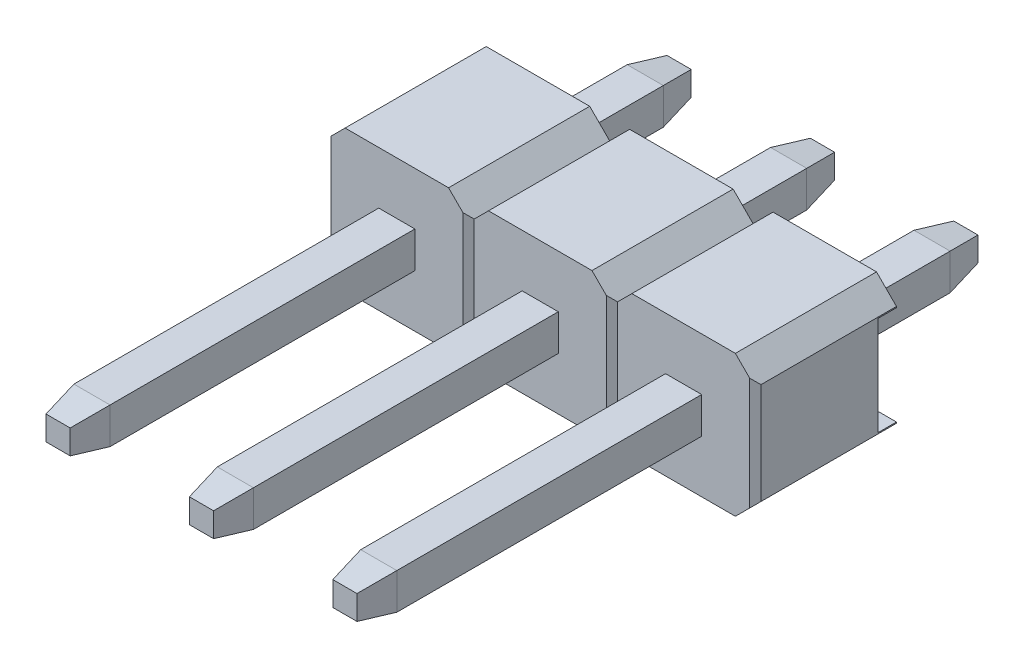
SolidWorks part; units mm, degrees
ref_plane "Front Plane" through (0, 0, 0) normal (0, 0, 1) x (1, 0, 0)
ref_plane "Top Plane" through (0, 0, 0) normal (0, 1, 0) x (1, 0, 0)
ref_plane "Right Plane" through (0, 0, 0) normal (1, 0, 0) x (0, 0, -1)
sketch "Sketch1" plane through (0, 0, 0) normal (0, 0, 1) x (1, 0, 0)
  line L0 (-1.27, 0.8964) -> (-0.9164, 1.25)
  line L1 (-0.9164, 1.25) -> (0.9164, 1.25)
  line L2 (-1.27, 0.8964) -> (-1.27, -0.8964)
  line L3 (-0.9164, -1.25) -> (0.9164, -1.25)
  line L4 (1.27, 0.8964) -> (1.27, -0.8964)
  line L5 (-1.27, -0.8964) -> (-0.9164, -1.25)
  line L6 (0.9164, -1.25) -> (1.27, -0.8964)
  line L7 (1.27, 0.8964) -> (0.9164, 1.25)
  point P0 (1.27, -1.25)
  point P7 (-1.27, 1.25)
  point P10 (-1.27, -1.25)
  point P15 (1.27, 1.25)
  dimension "D5" = 0.25
  dimension "D1" = 2.54
  dimension "D2" = 2.5
  dimension "D3" = 1.27
  dimension "D4" = 1.25
  dimension "D6" = 0.25
  dimension "D7" = 0.25
  dimension "D8" = 0.25
extrude "Extrude1" add sketch "Sketch1" along normal blind 1.25 and the other way blind 1.25
sketch "Sketch4" plane through (0, 0, 0) normal (0, 1, 0) x (1, 0, 0)
  line L0 (-1.27, -1.15) -> (-1.17, -1.25)
  line L1 (-1.17, -1.25) -> (-1.27, -1.25)
  line L2 (-1.27, -1.25) -> (-1.27, -1.15)
  line L3 (1.17, -1.25) -> (1.27, -1.15)
  line L4 (1.27, -1.15) -> (1.27, -1.25)
  line L5 (1.27, -1.25) -> (1.17, -1.25)
extrude "Cut-Extrude3" cut sketch "Sketch4" against normal through all and the other way through all
pattern_linear "LPattern4" count 3 spacing 2.54 along (-1, 0, 0) of "Extrude1", "Cut-Extrude3"
sketch "Sketch2" plane through (0, 0, 0) normal (1, 0, 0) x (0, -1, 0)
  line L1 (-0.8764, 1.25) -> (0.8764, 1.25)
  line L2 (-0.8764, 1.25) -> (-0.8764, 0.92)
  line L3 (-0.8764, 0.92) -> (0.8764, 0.92)
  line L4 (0.8764, 1.25) -> (0.8764, 0.92)
  dimension "D1" = 0.33
extrude "Cut-Extrude1" cut sketch "Sketch2" against normal through all and the other way through all
sketch "Sketch3" plane through (0, 0, 0) normal (1, 0, 0) x (0, 0, -1)
  line L0 (-7.25, 0) -> (3.75, 0)
  line L1 (1.25, 1.25) -> (1.25, 0.8964) construction
  dimension "D1" = 6
  dimension "D2" = 2.5
extrude "Extrude-Thin1" add sketch "Sketch3" along normal blind 0.32 and the other way blind 0.32 thin thin type mid plane wall 0.64
pattern_linear "LPattern5" count 1 spacing 2.54 along (1, 0, 0) count 3 spacing 2.54 along (-1, 0, 0) of "Extrude-Thin1"
chamfer "Chamfer2" distance 0.6 angle 10 24 edges at (0.32, 0, 7.25) (0, -0.32, 7.25) (-0.32, 0, 7.25) (0, 0.32, 7.25) (0.32, 0, -3.75) (-0.32, 0, -3.75) (-4.76, 0, -3.75) (-5.4, 0, -3.75) (-2.22, 0, -3.75) (-2.86, 0, -3.75) (-2.22, 0, 7.25) (-2.54, -0.32, 7.25) (-2.86, 0, 7.25) (-2.54, 0.32, 7.25) (-4.76, 0, 7.25) (-5.08, -0.32, 7.25) (-5.4, 0, 7.25) (-5.08, 0.32, 7.25) (-2.54, 0.32, -3.75) (-2.54, -0.32, -3.75) (0, 0.32, -3.75) (0, -0.32, -3.75) (-5.08, 0.32, -3.75) (-5.08, -0.32, -3.75) first distance on face at (0.32, 0, 4.25) first distance on face at (0, -0.32, 4.25) first distance on face at (-0.32, 0, 4.25) first distance on face at (0, 0.32, 4.25) first distance on face at (0.32, 0, -2.335) first distance on face at (-0.32, 0, -2.335) first distance on face at (-4.76, 0, -2.335) first distance on face at (-5.4, 0, -2.335) first distance on face at (-2.22, 0, -2.335) first distance on face at (-2.86, 0, -2.335) first distance on face at (-2.22, 0, 4.25) first distance on face at (-2.54, -0.32, 4.25) first distance on face at (-2.86, 0, 4.25) first distance on face at (-2.54, 0.32, 4.25) first distance on face at (-4.76, 0, 4.25) first distance on face at (-5.08, -0.32, 4.25) first distance on face at (-5.4, 0, 4.25) first distance on face at (-5.08, 0.32, 4.25) first distance on face at (-2.54, 0.32, -2.335) first distance on face at (-2.54, -0.32, -2.335) first distance on face at (0, 0.32, -2.335) first distance on face at (0, -0.32, -2.335) first distance on face at (-5.08, 0.32, -2.335) first distance on face at (-5.08, -0.32, -2.335)
ref_plane "Board Plane" through (0, 0, -1.5) normal (0, 0, 1) x (1, 0, 0)
sketch "Component_Outline" plane through (0, 0, -1.5) normal (0, 0, 1) x (1, 0, 0)
  line L0 (1.27, 0.8964) -> (1.27, -0.8964)
  line L1 (1.27, -0.8964) -> (0.9164, -1.25)
  line L2 (0.9164, -1.25) -> (-0.9164, -1.25)
  line L3 (-0.9164, -1.25) -> (-1.27, -0.8964)
  line L4 (-1.27, -0.8964) -> (-1.6236, -1.25)
  line L5 (-1.6236, -1.25) -> (-3.4564, -1.25)
  line L6 (-3.4564, -1.25) -> (-3.81, -0.8964)
  line L7 (-3.81, -0.8964) -> (-4.1636, -1.25)
  line L8 (-4.1636, -1.25) -> (-5.9964, -1.25)
  line L9 (-5.9964, -1.25) -> (-6.35, -0.8964)
  line L10 (-6.35, 0.8964) -> (-6.35, -0.8964)
  line L23 (-6.35, 0.8964) -> (-5.9964, 1.25)
  line L24 (-5.9964, 1.25) -> (-4.1636, 1.25)
  line L25 (-4.1636, 1.25) -> (-3.81, 0.8964)
  line L26 (-3.81, 0.8964) -> (-3.4564, 1.25)
  line L27 (-3.4564, 1.25) -> (-1.6236, 1.25)
  line L28 (-1.6236, 1.25) -> (-1.27, 0.8964)
  line L29 (-1.27, 0.8964) -> (-0.9164, 1.25)
  line L30 (-0.9164, 1.25) -> (0.9164, 1.25)
  line L31 (0.9164, 1.25) -> (1.27, 0.8964)
  point P64 (0, 0)
